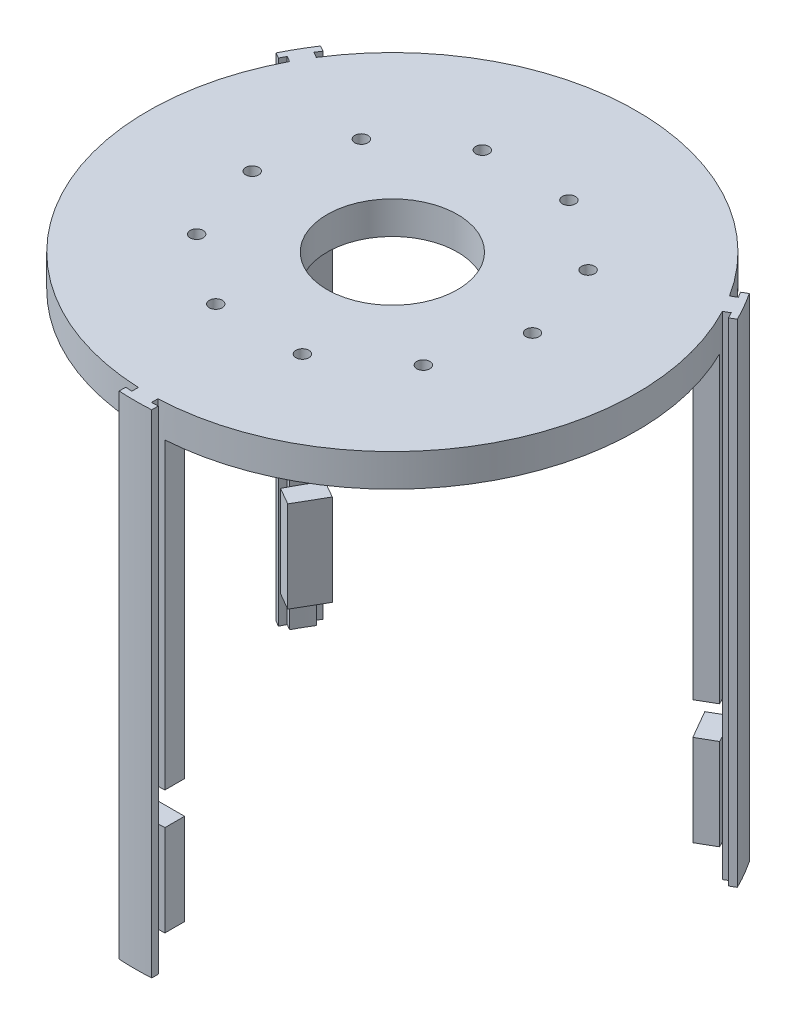
SolidWorks part; units mm, degrees
ref_plane "Front Plane" through (0, 0, 0) normal (0, 0, 1) x (1, 0, 0)
ref_plane "Top Plane" through (0, 0, 0) normal (0, 1, 0) x (1, 0, 0)
ref_plane "Right Plane" through (0, 0, 0) normal (1, 0, 0) x (0, 0, -1)
sketch "Sketch1" plane through (0, 0, 0) normal (0, 1, 0) x (1, 0, 0)
  circle A0 centre (0, 0) radius 37.5
  dimension "D1" = 75
extrude "Boss-Extrude1" add sketch "Sketch1" against normal blind 5
sketch "Sketch2" plane through (0, 0, 0) normal (0, 1, 0) x (1, 0, 0)
  line L0 (-2.75, 0) -> (2.75, 0) construction
  line L1 (0, 39.8902) -> (0, -39.5701) construction
  line L2 (0, -2.75) -> (0, 2.75) construction
  line L4 (-39.7283, 0) -> (39.0263, 0) construction
  circle A0 centre (-21.5, 0) radius 1
  circle A1 centre (-17.3939, 12.6374) radius 1
  circle A2 centre (-6.6439, 20.4477) radius 1
  circle A3 centre (6.6439, 20.4477) radius 1
  circle A4 centre (17.3939, 12.6374) radius 1
  circle A5 centre (21.5, 0) radius 1
  circle A6 centre (17.3939, -12.6374) radius 1
  circle A7 centre (6.6439, -20.4477) radius 1
  circle A8 centre (-6.6439, -20.4477) radius 1
  circle A9 centre (-17.3939, -12.6374) radius 1
  dimension "D1" = 10
  dimension "D2" = 43
extrude "Cut-Extrude1" cut sketch "Sketch2" against normal up to next
sketch "Sketch3" plane through (0, -5, 0) normal (0, -1, 0) x (1, 0, 0)
  line L0 (-2.4705, 37.4185) -> (-2.4705, 34.4146)
  line L1 (-2.4705, 34.4146) -> (2.5295, 34.4146)
  line L2 (2.5295, 34.4146) -> (2.5295, 37.4146)
  line L3 (33.6406, -16.5698) -> (31.0391, -15.0678)
  line L4 (31.0391, -15.0678) -> (28.5391, -19.3979)
  line L5 (28.5391, -19.3979) -> (31.1372, -20.8979)
  line L6 (-31.1702, -20.8488) -> (-28.5687, -19.3468)
  line L7 (-28.5687, -19.3468) -> (-31.0687, -15.0167)
  line L8 (-31.0687, -15.0167) -> (-33.6668, -16.5167)
  arc A0 (2.5295, 37.4146) -> (-2.4705, 37.4185) centre (0, 0) ccw
  arc A1 (31.1372, -20.8979) -> (33.6406, -16.5698) centre (0, 0) ccw
  arc A2 (-33.6668, -16.5167) -> (-31.1702, -20.8488) centre (0, 0) ccw
  dimension "D1" = 3
  dimension "D2" = 3
  dimension "D3" = 5
extrude "Boss-Extrude2" add sketch "Sketch3" along normal blind 65.5
sketch "Sketch4" plane through (0, -5, 0) normal (0, -1, 0) x (1, 0, 0)
  line L0 (-15.5255, 11.28) -> (-15.2841, 13.5767)
  line L1 (-19.1906, 0) -> (-20.3453, 2)
  line L2 (-20.3453, 2) -> (-22.6547, 2)
  line L3 (-22.6547, 2) -> (-23.8094, 0)
  line L4 (-23.8094, 0) -> (-22.6547, -2)
  line L5 (-22.6547, -2) -> (-20.3453, -2)
  line L6 (-20.3453, -2) -> (-19.1906, 0)
  line L7 (-15.2841, 13.5767) -> (-17.1525, 14.9341)
  line L8 (-17.1525, 14.9341) -> (-19.2622, 13.9948)
  line L9 (-19.2622, 13.9948) -> (-19.5036, 11.6981)
  line L10 (-19.5036, 11.6981) -> (-17.6353, 10.3406)
  line L11 (-17.6353, 10.3406) -> (-15.5255, 11.28)
  line L12 (-5.9302, 18.2513) -> (-4.3849, 19.9676)
  line L13 (-4.3849, 19.9676) -> (-5.0986, 22.1639)
  line L14 (-5.0986, 22.1639) -> (-7.3575, 22.6441)
  line L15 (-7.3575, 22.6441) -> (-8.9028, 20.9279)
  line L16 (-8.9028, 20.9279) -> (-8.1892, 18.7315)
  line L17 (-8.1892, 18.7315) -> (-5.9302, 18.2513)
  line L18 (5.9302, 18.2513) -> (8.1892, 18.7315)
  line L19 (8.1892, 18.7315) -> (8.9028, 20.9279)
  line L20 (8.9028, 20.9279) -> (7.3575, 22.6441)
  line L21 (7.3575, 22.6441) -> (5.0986, 22.1639)
  line L22 (5.0986, 22.1639) -> (4.3849, 19.9676)
  line L23 (4.3849, 19.9676) -> (5.9302, 18.2513)
  line L24 (15.5255, 11.28) -> (17.6353, 10.3406)
  line L25 (17.6353, 10.3406) -> (19.5036, 11.6981)
  line L26 (19.5036, 11.6981) -> (19.2622, 13.9948)
  line L27 (19.2622, 13.9948) -> (17.1525, 14.9341)
  line L28 (17.1525, 14.9341) -> (15.2841, 13.5767)
  line L29 (15.2841, 13.5767) -> (15.5255, 11.28)
  line L30 (19.1906, 0) -> (20.3453, -2)
  line L31 (20.3453, -2) -> (22.6547, -2)
  line L32 (22.6547, -2) -> (23.8094, 0)
  line L33 (23.8094, 0) -> (22.6547, 2)
  line L34 (22.6547, 2) -> (20.3453, 2)
  line L35 (20.3453, 2) -> (19.1906, 0)
  line L36 (15.5255, -11.28) -> (15.2841, -13.5767)
  line L37 (15.2841, -13.5767) -> (17.1525, -14.9341)
  line L38 (17.1525, -14.9341) -> (19.2622, -13.9948)
  line L39 (19.2622, -13.9948) -> (19.5036, -11.6981)
  line L40 (19.5036, -11.6981) -> (17.6353, -10.3406)
  line L41 (17.6353, -10.3406) -> (15.5255, -11.28)
  line L42 (5.9302, -18.2513) -> (4.3849, -19.9676)
  line L43 (4.3849, -19.9676) -> (5.0986, -22.1639)
  line L44 (5.0986, -22.1639) -> (7.3575, -22.6441)
  line L45 (7.3575, -22.6441) -> (8.9028, -20.9279)
  line L46 (8.9028, -20.9279) -> (8.1892, -18.7315)
  line L47 (8.1892, -18.7315) -> (5.9302, -18.2513)
  line L48 (-5.9302, -18.2513) -> (-8.1892, -18.7315)
  line L49 (-8.1892, -18.7315) -> (-8.9028, -20.9279)
  line L50 (-8.9028, -20.9279) -> (-7.3575, -22.6441)
  line L51 (-7.3575, -22.6441) -> (-5.0986, -22.1639)
  line L52 (-5.0986, -22.1639) -> (-4.3849, -19.9676)
  line L53 (-4.3849, -19.9676) -> (-5.9302, -18.2513)
  line L54 (-15.5255, -11.28) -> (-17.6353, -10.3406)
  line L55 (-17.6353, -10.3406) -> (-19.5036, -11.6981)
  line L56 (-19.5036, -11.6981) -> (-19.2622, -13.9948)
  line L57 (-19.2622, -13.9948) -> (-17.1525, -14.9341)
  line L58 (-17.1525, -14.9341) -> (-15.2841, -13.5767)
  line L59 (-15.2841, -13.5767) -> (-15.5255, -11.28)
  circle A0 centre (-21.5, 0) radius 2 construction
  dimension "D1" = 10
extrude "Cut-Extrude2" cut sketch "Sketch4" against normal blind 1.6
sketch "Sketch5" plane through (0, 0, 0) normal (0, 1, 0) x (1, 0, 0)
  line L0 (-2.4982, -38.4161) -> (-2.4982, -39.4209)
  line L1 (2.5018, -38.4158) -> (2.5018, -39.4207)
  line L2 (1.5018, -38.4679) -> (1.5018, -37.4699)
  line L3 (-1.4982, -38.468) -> (-1.4982, -37.4701)
  line L4 (-32.0202, 21.3715) -> (-32.8904, 21.8739)
  line L5 (-34.52, 17.0413) -> (-35.3902, 17.5437)
  line L6 (-34.0651, 17.9333) -> (-33.2008, 17.4343)
  line L7 (-32.5652, 20.5315) -> (-31.7009, 20.0325)
  line L8 (34.5184, 17.0446) -> (35.3886, 17.547)
  line L9 (32.0182, 21.3746) -> (32.8884, 21.877)
  line L10 (32.5633, 20.5346) -> (31.699, 20.0356)
  line L11 (34.0634, 17.9366) -> (33.1991, 17.4376)
  arc A0 (-2.4982, -39.4209) -> (2.5018, -39.4207) centre (0, 0) ccw
  arc A1 (-1.4982, -37.4701) -> (1.5018, -37.4699) centre (0, 0) ccw
  arc A2 (2.5018, -38.4158) -> (1.5018, -38.4679) centre (0, 0) cw
  arc A3 (-2.4982, -38.4161) -> (-1.4982, -38.468) centre (0, 0) ccw
  arc A4 (-32.8904, 21.8739) -> (-35.3902, 17.5437) centre (0, 0) ccw
  arc A5 (-31.7009, 20.0325) -> (-33.2008, 17.4343) centre (0, 0) ccw
  arc A6 (-34.52, 17.0413) -> (-34.0651, 17.9333) centre (0, 0) cw
  arc A7 (-32.0202, 21.3715) -> (-32.5652, 20.5315) centre (0, 0) ccw
  arc A8 (35.3886, 17.547) -> (32.8884, 21.877) centre (0, 0) ccw
  arc A9 (33.1991, 17.4376) -> (31.699, 20.0356) centre (0, 0) ccw
  arc A10 (32.0182, 21.3746) -> (32.5633, 20.5346) centre (0, 0) cw
  arc A11 (34.5184, 17.0446) -> (34.0634, 17.9366) centre (0, 0) ccw
  circle A12 centre (0, 0) radius 37.5 construction
  dimension "D1" = 3
  dimension "D2" = 5
  dimension "D3" = 2
  dimension "D4" = 1.0049
  dimension "D5" = 1
extrude "Boss-Extrude3" add sketch "Sketch5" against normal blind 75.5
sketch "Sketch6" plane through (0, 0, 0) normal (0, 1, 0) x (1, 0, 0)
  circle A0 centre (0, 0) radius 10
extrude "Cut-Extrude3" cut sketch "Sketch6" against normal up to next
sketch "Sketch7" plane through (0, 0, 0) normal (1, 0, 0) x (0, 0, -1)
  line L0 (0, 41.25) -> (0, -41.25) construction
  line L1 (0, -51.5) -> (-37.5, -51.5)
  line L2 (0, -51.5) -> (0, -56.5)
  line L3 (0, -56.5) -> (-37.5, -56.5)
  line L4 (-37.5, -51.5) -> (-37.5, -56.5)
  line L6 (-34.4146, -70.5) -> (-37.4146, -70.5) construction
  line L7 (0, -27.0167) -> (0, -72.0117) construction
  dimension "D1" = 37.5
  dimension "D2" = 5
  dimension "D3" = 14
revolve "Cut-Revolve1" cut sketch "Sketch7" angle 360 about L7
